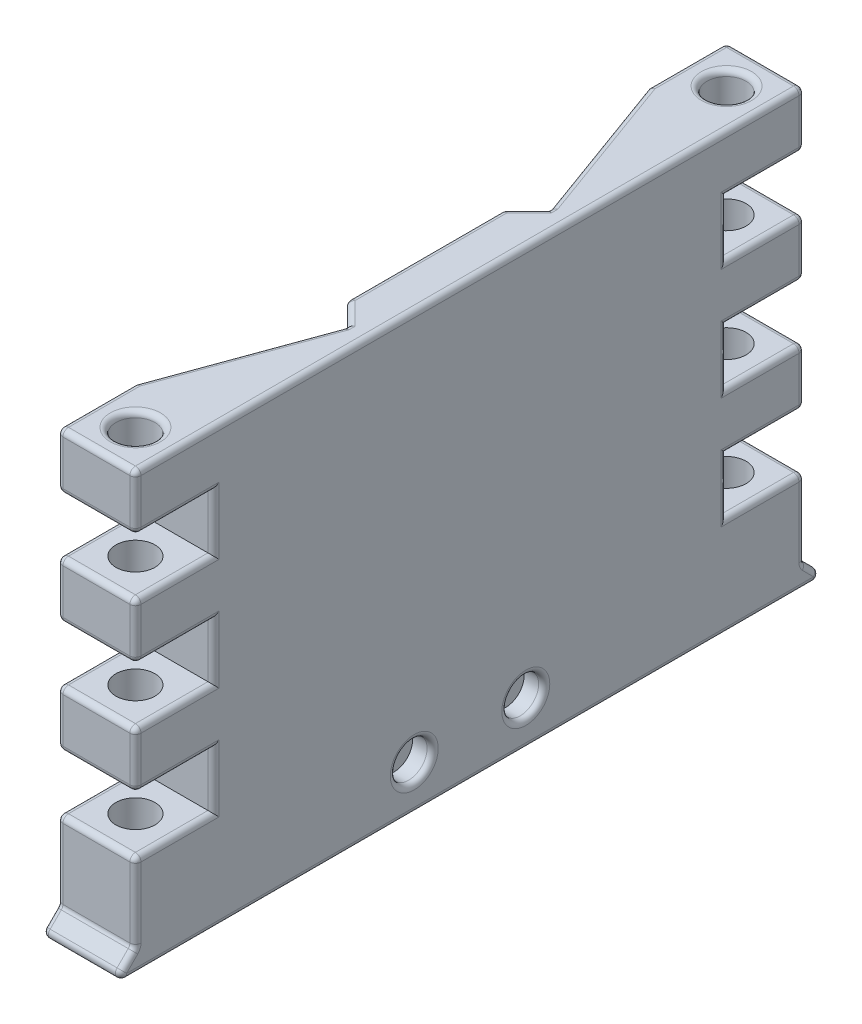
SolidWorks part; units mm, degrees
ref_plane "Front Plane" through (0, 0, 0) normal (0, 0, 1) x (1, 0, 0)
ref_plane "Top Plane" through (0, 0, 0) normal (0, 1, 0) x (1, 0, 0)
ref_plane "Right Plane" through (0, 0, 0) normal (1, 0, 0) x (0, 0, -1)
sketch "Sketch1" plane through (0, 0, 0) normal (1, 0, 0) x (0, 0, -1)
  line L1 (-15, -19.5) -> (15, -19.5)
  line L2 (-15, -5.5) -> (-15, -0.5)
  line L3 (-8, 19.5) -> (15, 19.5)
  line L4 (15, -19.5) -> (15, 19.5)
  line L5 (-15, -19.5) -> (15, 19.5) construction
  line L6 (-15, 19.5) -> (15, -19.5) construction
  line L8 (-17, -19.5) -> (-15, -19.5)
  line L12 (-8, 19.5) -> (-8, 14.5) construction
  line L13 (-8, 14.5) -> (-15, 14.5)
  line L14 (-8, 14.5) -> (-8, 9.5)
  line L15 (-8, 9.5) -> (-15, 9.5)
  line L16 (-8, 9.5) -> (-8, 4.5) construction
  line L17 (-8, 4.5) -> (-8, -0.5)
  line L18 (-8, -0.5) -> (-8, -5.5) construction
  line L19 (-8, -5.5) -> (-8, -10.5)
  line L20 (-8, 19.5) -> (-15, 19.5)
  line L21 (-15, 14.5) -> (-15, 19.5)
  line L22 (-8, -10.5) -> (-15, -10.5)
  line L23 (-8, -5.5) -> (-15, -5.5)
  line L24 (-8, -0.5) -> (-15, -0.5)
  line L25 (-8, 4.5) -> (-15, 4.5)
  line L26 (-15, 4.5) -> (-15, 9.5)
  line L43 (-15, -17.5) -> (-15, -10.5)
  line L44 (-15, -17.5) -> (-17, -19.5)
  line L45 (10, -19.5) -> (10, -15.5) construction
  line L46 (10, -15.5) -> (15, -15.5) construction
  circle A0 centre (10, -15.5) radius 1.65
  point P0 (0, 0)
  point P12 (0, 0)
  dimension "D9" = 3.3
  dimension "D1" = 39
  dimension "D2" = 30
  dimension "D3" = 2
  dimension "D4" = 7
  dimension "D5" = 5
  dimension "D6" = 2
  dimension "D7" = 4
  dimension "D8" = 5
extrude "Boss-Extrude1" add sketch "Sketch1" along normal blind 7 contours L13 L12 L3 L2 region at (0, -0.1087, -1.0304)
extrude "Boss-Extrude2" add sketch "Sketch1<3>" along normal blind 5.2 contours A0
sketch "Sketch1<3>" plane through (0, 0, 0) normal (1, 0, 0) x (0, 0, -1) same geometry as "Sketch1"
sketch "Sketch7" plane through (0, -19.5, 0) normal (0, -1, 0) x (1, 0, 0)
  line L1 (0, 17) -> (0, -15) construction
  line L2 (3.5, 11.5) -> (3.5, 15) construction
  line L3 (7, 15) -> (7, 8) construction
  line L4 (7, 8) -> (0, 8) construction
  line L5 (0, 8) -> (0, 15) construction
  line L6 (3.5, 15) -> (3.5, 17) construction
  line L7 (3.5, 15) -> (7, 15) construction
  line L8 (7, 8) -> (0, 15) construction
  line L9 (7, 17) -> (0, 17) construction
  line L10 (0.675, 9.869) -> (3.5, 8.238)
  line L11 (3.5, 8.238) -> (6.325, 9.869)
  line L12 (6.325, 9.869) -> (6.325, 13.131)
  line L13 (6.325, 13.131) -> (3.5, 14.762)
  line L14 (3.5, 14.762) -> (0.675, 13.131)
  line L15 (0.675, 13.131) -> (0.675, 9.869)
  line L16 (3.5, 8.238) -> (3.5, 8) construction
  circle A0 centre (3.5, 11.5) radius 1.75
  circle A1 centre (3.5, 11.5) radius 2.825 construction
  dimension "D4" = 5.65
  dimension "D5" = 3.5
  dimension "D1" = 2
  dimension "D2" = 7
  dimension "D3" = 7
extrude "Cut-Extrude3" cut sketch "Sketch7" against normal through all both and the other way through all contours A0 region at (3.5, -19.5, 11.5)
extrude "Cut-Extrude4" cut sketch "Sketch7<3>" against normal blind 3 and the other way through all contours L14 L15 L10 L11 L12 L13 A0 region at (0.7613, -19.5, 11.5)
sketch "Sketch7<3>" plane through (0, -19.5, 0) normal (0, -1, 0) x (1, 0, 0) same geometry as "Sketch7"
sketch "Sketch8" plane through (0, 19.5, 0) normal (0, 1, 0) x (1, 0, 0)
  line L0 (0, -8) -> (5, 5.7374)
  line L1 (0, -15) -> (0, 15) construction
  line L3 (7, 15) -> (0, 15) construction
  line L4 (0, -8) -> (0, 15)
  line L5 (0, 15) -> (5, 15) construction
  line L6 (5, 5.7374) -> (5, 6)
  line L7 (5, 6) -> (3, 8)
  line L8 (3, 8) -> (3, 15)
  line L9 (7, -15) -> (7, 15) construction
  line L10 (3, 15) -> (0, 15)
  dimension "D1" = 2
  dimension "D2" = 7
  dimension "D3" = 2
  dimension "D4" = 200
  dimension "D5" = 2
  dimension "D6" = 7
  dimension "D7" = 135
extrude "Cut-Extrude5" cut sketch "Sketch8" against normal through all
mirror "Mirror2" about plane through (7, 0, -15) normal (0, 0, 1) of bodies 111 109
fillet "Fillet1" radius 0.5 94 edges at (2.5, -19.5, 1.1313) (2.5, -19.5, -31.1313) (0, -18.5, -46) (0, -18.5, 16) (3.5, -17.5, -45) (3.5, -10.5, -45) (0, -14, -45) (3.5, -5.5, -45) (3.5, -0.5, -45) (0, -3, -45) (3.5, 4.5, -45) (3.5, 9.5, -45) (0, 7, -45) (3.5, 14.5, -45) (0, 17, -45) (7, -10.5, 11.5) (7, -8, 8) (7, -5.5, 11.5) (7, -0.5, 11.5) (7, 2, 8) (7, 4.5, 11.5) (7, 9.5, 11.5) (7, 12, 8) (7, 14.5, 11.5) (7, 17, -45) (7, 14.5, -41.5) (7, 12, -38) (7, 9.5, -41.5) (7, 7, -45) (7, 4.5, -41.5) (7, 2, -38) (7, -0.5, -41.5) (7, -3, -45) (7, -5.5, -41.5) (7, -8, -38) (7, -10.5, -41.5) (7, -14, -45) (7, -18.5, -46) (7, -19.5, -15) (7, -18.5, 16) (3.5, -10.5, 15) (7, -14, 15) (3.5, -17.5, 15) (0, -14, 15) (3.5, -0.5, 15) (7, -3, 15) (3.5, -5.5, 15) (0, -3, 15) (3.5, 9.5, 15) (7, 7, 15) (3.5, 4.5, 15) (0, 7, 15) (7, 17, 15) (3.5, 14.5, 15) (0, 17, 15) (3.5, 19.5, -39.75) (3.5, 19.5, 9.75) (2.5, 19.5, -31.1313) (0, 19.5, -41.5) (3.5, 19.5, -45) (7, 19.5, -15) (3.5, 19.5, 15) (0, 19.5, 11.5) (2.5, 19.5, 1.1313) (0, -19.5, 12.5) (0, -19.5, -42.5) (0, 14.5, 11.5) (0, 9.5, 11.5) (0, 4.5, 11.5) (0, -0.5, 11.5) (0, -5.5, 11.5) (0, -10.5, 11.5) (0, -10.5, -41.5) (0, -5.5, -41.5) (0, -0.5, -41.5) (0, 4.5, -41.5) (0, 9.5, -41.5) (0, 14.5, -41.5) (3.5, -19.5, 17) (3.5, -19.5, -47) (7, -15.5, -18.35) (7, -15.5, -11.65) (5, 19.5, -5.8687) (4, 19.5, -7) (3, 19.5, -15) (4, 19.5, -23) (5, 19.5, -24.1313) (3, 0, -8) (3, -19.5, -15) (3, 0, -22) (5, -19.5, -24.1313) (4, -19.5, -23) (4, -19.5, -7) (5, -19.5, -5.8687)
